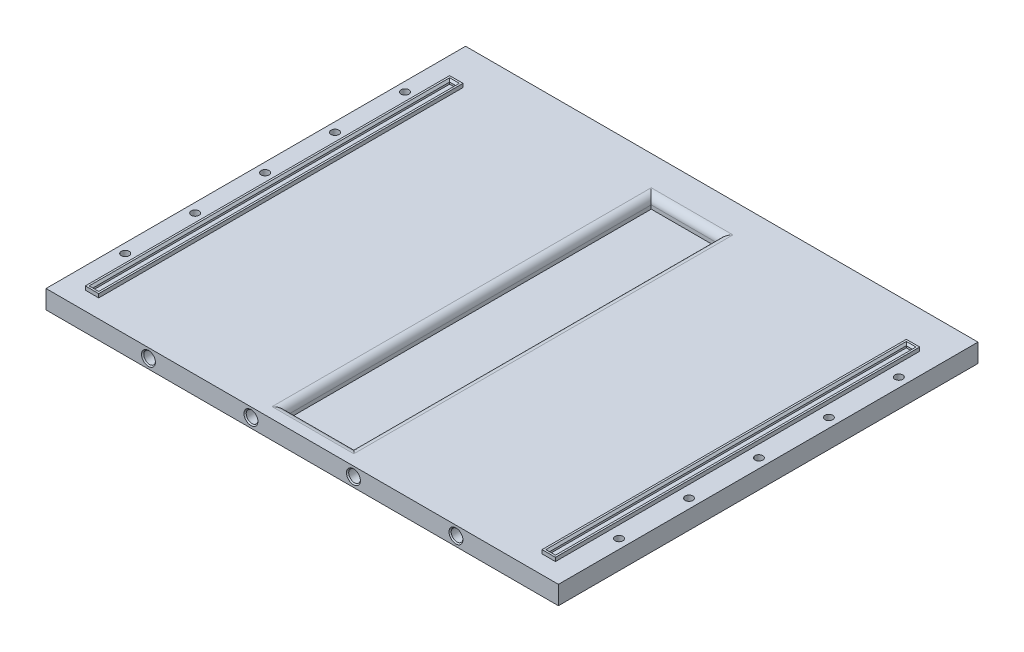
SolidWorks part; units mm, degrees
ref_plane "Спереди" through (0, 0, 0) normal (0, 0, 1) x (1, 0, 0)
ref_plane "Сверху" through (0, 0, 0) normal (0, 1, 0) x (1, 0, 0)
ref_plane "Справа" through (0, 0, 0) normal (1, 0, 0) x (0, 0, -1)
sketch "Эскиз1" plane through (0, 0, 0) normal (0, 1, 0) x (1, 0, 0)
  line L5 (-69, -56.5) -> (69, -56.5)
  line L6 (-69, -56.5) -> (-69, 56.5)
  line L7 (-69, 56.5) -> (69, 56.5)
  line L8 (69, -56.5) -> (69, 56.5)
  line L9 (-69, -56.5) -> (69, 56.5) construction
  line L10 (-69, 56.5) -> (69, -56.5) construction
  point P0 (0, 0)
  dimension "D1" = 113
  dimension "D2" = 138
extrude "Основание" add sketch "Эскиз1" along normal blind 5
sketch "Эскиз6" plane through (0, 0, 0) normal (0, -1, 0) x (1, 0, 0)
  line L0 (0, 45.5668) -> (0, -26.923) construction
  line L1 (-15.8226, 0) -> (3.0664, 0) construction
  line L2 (-37, 37) -> (0, 37) construction
  line L3 (-47, 47) -> (-27, 47)
  line L4 (-47, 47) -> (-47, 27)
  line L5 (-47, 27) -> (-27, 27)
  line L6 (-27, 47) -> (-27, 27)
  line L7 (-47, 47) -> (-27, 27) construction
  line L8 (-47, 27) -> (-27, 47) construction
  line L9 (-37, 37) -> (-37, 0) construction
  line L10 (47, 47) -> (27, 47)
  line L11 (47, 47) -> (47, 27)
  line L12 (47, 27) -> (27, 27)
  line L13 (27, 47) -> (27, 27)
  line L14 (27, -47) -> (27, -27)
  line L15 (47, -27) -> (27, -27)
  line L16 (47, -47) -> (47, -27)
  line L17 (47, -47) -> (27, -47)
  line L18 (-47, -47) -> (-27, -47)
  line L19 (-47, -47) -> (-47, -27)
  line L20 (-47, -27) -> (-27, -27)
  line L21 (-27, -47) -> (-27, -27)
  point P1 (-37, 37)
  dimension "D1" = 20
  dimension "D2" = 37
extrude "Ножки" add sketch "Эскиз6" along normal blind 4
fillet "Скругление ножек" radius 2 16 edges at (-37, -4, 27) (-47, -4, 37) (-37, -4, 47) (-27, -4, 37) (-37, -4, -27) (-27, -4, -37) (-37, -4, -47) (-47, -4, -37) (27, -4, -37) (37, -4, -27) (47, -4, -37) (37, -4, -47) (37, -4, 27) (27, -4, 37) (37, -4, 47) (47, -4, 37)
fillet "Скругление3" radius 2 48 edges at (46.4142, -3.4142, 27.5858) (27.5858, -3.4142, 27.5858) (46.4142, -3.4142, 46.4142) (27.5858, -3.4142, 46.4142) (-46.4142, -3.4142, 46.4142) (27.5858, -3.4142, -27.5858) (-46.4142, -3.4142, 27.5858) (-27.5858, -3.4142, 27.5858) (-27.5858, -3.4142, 46.4142) (27.5858, -3.4142, -46.4142) (46.4142, -3.4142, -46.4142) (46.4142, -3.4142, -27.5858) (-27.5858, -3.4142, -46.4142) (-46.4142, -3.4142, -46.4142) (-27.5858, -3.4142, -27.5858) (-46.4142, -3.4142, -27.5858) (37, 0, 27) (47, 0, 37) (47, -1, 27) (27, 0, 37) (27, -1, 27) (37, 0, 47) (47, -1, 47) (27, -1, 47) (-47, 0, 37) (-37, 0, 47) (-47, -1, 47) (27, 0, -37) (37, 0, -27) (27, -1, -27) (-37, 0, 27) (-47, -1, 27) (-27, 0, 37) (-27, -1, 27) (-27, -1, 47) (37, 0, -47) (27, -1, -47) (47, 0, -37) (47, -1, -47) (47, -1, -27) (-37, 0, -47) (-27, 0, -37) (-27, -1, -47) (-47, 0, -37) (-47, -1, -47) (-37, 0, -27) (-27, -1, -27) (-47, -1, -27)
sketch "Эскиз2" plane through (0, 5, 0) normal (0, 1, 0) x (1, 0, 0)
  line L0 (0, 0) -> (0, -25.5598) construction
  line L1 (-61.5, 37.0772) -> (-61.5, 5.6487) construction
  line L2 (-21.6597, -2.55) -> (12.5108, -2.55) construction
  line L3 (-59.7, 46.5) -> (-63.3, 46.5)
  line L4 (-63.3, 46.5) -> (-63.3, -51.6)
  line L5 (-63.3, -2.55) -> (-62.3, -2.55)
  line L6 (-62.3, -50.6) -> (-62.3, 45.5)
  line L7 (-62.3, 45.5) -> (-60.7, 45.5)
  line L8 (-61.5, 45.5) -> (-61.5, 46.5)
  line L9 (-60.7, -50.6) -> (-60.7, 45.5)
  line L10 (-59.7, -2.55) -> (-60.7, -2.55)
  line L11 (-59.7, 46.5) -> (-59.7, -51.6)
  line L12 (-62.3, -50.6) -> (-60.7, -50.6)
  line L13 (-59.7, -51.6) -> (-63.3, -51.6)
  line L14 (-61.5, -50.6) -> (-61.5, -51.6)
  line L15 (61.5, -50.6) -> (61.5, -51.6)
  line L16 (59.7, -51.6) -> (63.3, -51.6)
  line L17 (62.3, -50.6) -> (60.7, -50.6)
  line L18 (59.7, 46.5) -> (59.7, -51.6)
  line L19 (59.7, -2.55) -> (60.7, -2.55)
  line L20 (60.7, -50.6) -> (60.7, 45.5)
  line L21 (61.5, 45.5) -> (61.5, 46.5)
  line L22 (62.3, 45.5) -> (60.7, 45.5)
  line L23 (62.3, -50.6) -> (62.3, 45.5)
  line L24 (63.3, -2.55) -> (62.3, -2.55)
  line L25 (63.3, 46.5) -> (63.3, -51.6)
  line L26 (59.7, 46.5) -> (63.3, 46.5)
  line L27 (-69, -56.5) -> (69, -56.5) construction
  dimension "D1" = 1
  dimension "D2" = 96.1
  dimension "D3" = 1.6
  dimension "D4" = 121.4
  dimension "D5" = 5.9
extrude "Ложемент материнской платы" add sketch "Эскиз2" along normal blind 1 contours L14 L12 L6 L5 L4 L13 | L7 L8 L3 L4 L5 L6 | L11 L3 L8 L7 L9 L10 | L12 L14 L13 L11 L10 L9 | L26 L21 L22 L23 L24 L25 | L26 L18 L19 L20 L22 L21 | L17 L20 L19 L18 L16 L15 | L25 L24 L23 L17 L15 L16 region at (-60.2144, 5, -22.3606) region at (-62.7856, 5, -22.3606) region at (-60.2144, 5, 27.4606) region at (-62.7856, 5, 27.4606) region at (62.7856, 5, 27.4606) region at (60.2144, 5, 27.4606) region at (62.7856, 5, -22.3606) region at (60.2144, 5, -22.3606)
fillet "Фаска первого ложемента" radius 0.5 4 edges at (-61.5, 6, -45.5) (-60.7, 6, 2.55) (-61.5, 6, 50.6) (-62.3, 6, 2.55) type face fillet profile chamfer first side face at (-61.5, 5.5, -45.5) first side face at (-61.5, 5.5, 50.6) first side face at (-60.7, 5.5, 2.55) first side face at (-62.3, 5.5, 2.55) second side face at (-61.5, 6, 2.55)
fillet "Фаска второго ложемента" radius 0.5 4 edges at (61.5, 6, 50.6) (60.7, 6, 2.55) (61.5, 6, -45.5) (62.3, 6, 2.55) type face fillet profile chamfer first side face at (61.5, 5.5, -45.5) first side face at (62.3, 5.5, 2.55) first side face at (60.7, 5.5, 2.55) first side face at (61.5, 5.5, 50.6) second side face at (61.5, 6, 2.55)
sketch "Эскиз3" plane through (0, 0, -56.5) normal (0, 0, -1) x (-1, 0, 0)
  line L0 (-69, 0) -> (69, 0) construction
  line L1 (-69, 5) -> (-69, 0) construction
  line L2 (-41.4, 2.5) -> (-69, 2.5) construction
  line L3 (41.4, 2.5) -> (69, 2.5) construction
  line L6 (69, 5) -> (69, 0) construction
  line L7 (-41.4, 2.5) -> (-13.8, 2.5) construction
  line L8 (-13.8, 2.5) -> (13.8, 2.5) construction
  line L9 (13.8, 2.5) -> (41.4, 2.5) construction
  circle A0 centre (-41.4, 2.5) radius 1.575
  circle A1 centre (-13.8, 2.5) radius 1.575
  circle A2 centre (13.8, 2.5) radius 1.575
  circle A3 centre (41.4, 2.5) radius 1.575
  dimension "D4" = 3.15
  dimension "D1" = 2.5
  dimension "D5" = 27.6
  dimension "D3" = 4
extrude "Крепежные отверсия передней и задней стенки" cut sketch "Эскиз3" against normal blind 4.2
ref_plane "Плоскость1" through (0, 0, 0) normal (0, 0, -1) x (-1, 0, 0)
mirror "Зеркальное отражение1" about plane through (0, 0, 0) normal (0, 0, -1) of "Крепежные отверсия передней и задней стенки"
chamfer "Фаска под запресовку" distance 0.3 angle 45 8 edges at (39.825, 2.5, -56.5) (-42.975, 2.5, -56.5) (-15.375, 2.5, -56.5) (12.225, 2.5, -56.5) (39.825, 2.5, 56.5) (12.225, 2.5, 56.5) (-15.375, 2.5, 56.5) (-42.975, 2.5, 56.5)
sketch "Эскиз4" plane through (0, 0, 0) normal (0, -1, 0) x (1, 0, 0)
  line L0 (0, 34.8353) -> (0, -23.754) construction
  line L1 (-66.5, 56.5) -> (-66.5, 37.6667) construction
  line L2 (-69, 56.5) -> (69, 56.5) construction
  line L3 (-66.5, 37.6667) -> (-66.5, 18.8333) construction
  line L4 (-66.5, 18.8333) -> (-66.5, 0) construction
  line L5 (-66.5, 0) -> (-66.5, -18.8333) construction
  line L6 (-66.5, -18.8333) -> (-66.5, -37.6667) construction
  line L7 (-66.5, -37.6667) -> (-66.5, -56.5) construction
  line L8 (69, -56.5) -> (-69, -56.5) construction
  line L9 (-69, -56.5) -> (-69, 56.5) construction
  circle A0 centre (-66.5, 37.6667) radius 1.05
  circle A1 centre (-66.5, 18.8333) radius 1.05
  circle A2 centre (-66.5, 0) radius 1.05
  circle A3 centre (-66.5, -18.8333) radius 1.05
  circle A4 centre (-66.5, -37.6667) radius 1.05
  circle A5 centre (66.5, -37.6667) radius 1.05
  circle A6 centre (66.5, -18.8333) radius 1.05
  circle A7 centre (66.5, 0) radius 1.05
  circle A8 centre (66.5, 18.8333) radius 1.05
  circle A9 centre (66.5, 37.6667) radius 1.05
  dimension "D3" = 2.1
  dimension "D2" = 2.5
  dimension "D1" = 5
extrude "Отверстия крепежных винтов" cut sketch "Эскиз4" against normal up to next
sketch "Эскиз5" plane through (0, 0, 0) normal (0, -1, 0) x (1, 0, 0)
  line L0 (0, 88.0608) -> (0, 29.4715) construction
  line L1 (-66.5, 56.5) -> (-66.5, 37.6667) construction
  line L2 (-66.5, 37.6667) -> (-66.5, 18.8333) construction
  line L3 (-66.5, 18.8333) -> (-66.5, 0) construction
  line L4 (-66.5, 0) -> (-66.5, -18.8333) construction
  line L5 (-66.5, -18.8333) -> (-66.5, -37.6667) construction
  line L6 (-66.5, -37.6667) -> (-66.5, -56.5) construction
  line L7 (69, -56.5) -> (-69, -56.5) construction
  line L8 (-69, 56.5) -> (69, 56.5) construction
  circle A0 centre (-66.5, 37.6667) radius 2
  circle A1 centre (-66.5, 18.8333) radius 2
  circle A2 centre (-66.5, 0) radius 2
  circle A3 centre (-66.5, -18.8333) radius 2
  circle A4 centre (-66.5, -37.6667) radius 2
  circle A5 centre (66.5, -37.6667) radius 2
  circle A6 centre (66.5, -18.8333) radius 2
  circle A7 centre (66.5, 0) radius 2
  circle A8 centre (66.5, 18.8333) radius 2
  circle A9 centre (66.5, 37.6667) radius 2
  circle A10 centre (-66.5, -37.6667) radius 1.05 construction
  dimension "D1" = 4
extrude "Потай головок винтов" cut sketch "Эскиз5" against normal blind 3
sketch "Эскиз8" plane through (0, 5, 0) normal (0, 1, 0) x (1, 0, 0)
  line L0 (-59.7, 46.5) -> (-38.3699, 46.5) construction
  line L1 (-59.7, -51.6) -> (-44.5392, -51.6) construction
  line L2 (-59.7, -51.6) -> (-63.3, -51.6) construction
  line L3 (-59.7, 46.5) -> (-63.3, 46.5) construction
  line L4 (0, 67.288) -> (0, -49932.712) construction
  line L5 (-9, 46.5) -> (9, 46.5)
  line L6 (-9, 46.5) -> (-9, -51.6)
  line L7 (-9, -51.6) -> (9, -51.6)
  line L8 (9, 46.5) -> (9, -51.6)
  point P16 (0, 46.5)
  dimension "D1" = 18
extrude "Ложемент для кабелей" cut sketch "Эскиз8" against normal blind 3
fillet "Скругление ложемента кабелей" radius 2 4 edges at (-9, 5, 2.55) (0, 5, -46.5) (9, 5, 2.55) (0, 5, 51.6)
